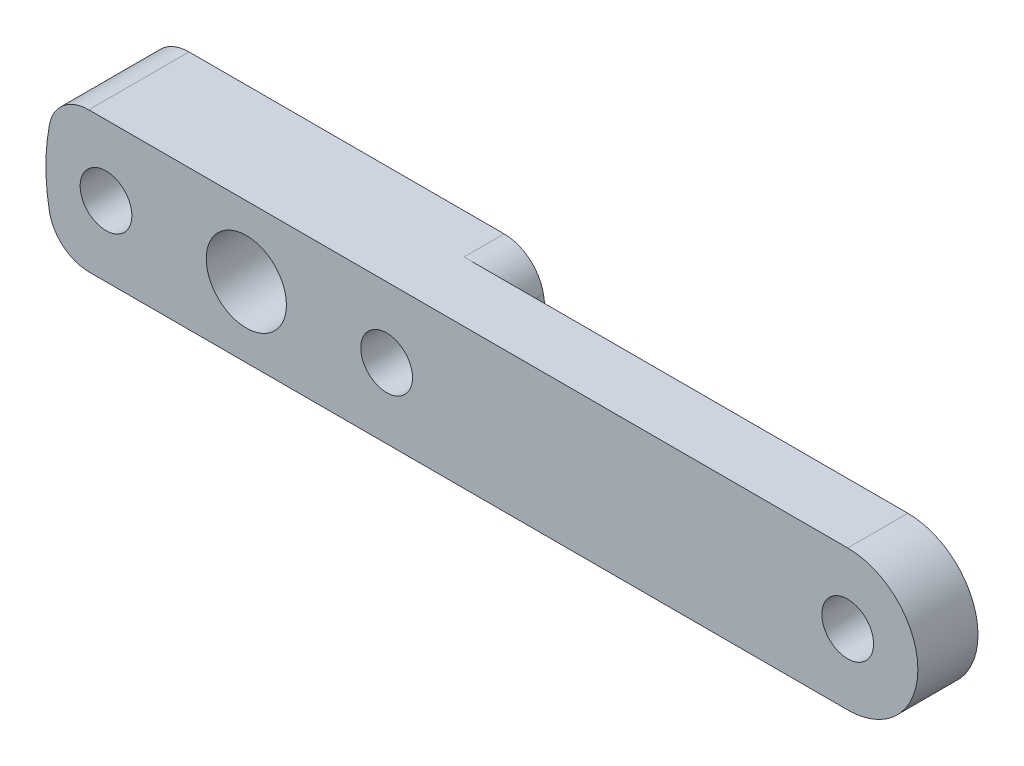
SolidWorks part; units mm, degrees
ref_plane "Front Plane" through (0, 0, 0) normal (0, 0, 1) x (1, 0, 0)
ref_plane "Top Plane" through (0, 0, 0) normal (0, 1, 0) x (1, 0, 0)
ref_plane "Right Plane" through (0, 0, 0) normal (1, 0, 0) x (0, 0, -1)
sketch "Sketch1" plane through (0, 0, 0) normal (0, 0, 1) x (1, 0, 0)
  line L0 (-9.3675, 3.5) -> (30, 3.5)
  line L1 (30, -3.5) -> (-9.3675, -3.5)
  line L2 (-7, 0) -> (7, 0) construction
  arc A0 (-9.3675, -3.5) -> (-9.3675, 3.5) centre (0, 0) cw
  arc A1 (30, 3.5) -> (30, -3.5) centre (30, 0) cw
  circle A2 centre (-7, 0) radius 1.29
  circle A3 centre (7, 0) radius 1.29
  circle A4 centre (30, 0) radius 1.29
  circle A5 centre (0, 0) radius 2
  point P6 (-10, 0)
  point P12 (0, 0)
  dimension "D1" = 10
  dimension "D2" = 7
  dimension "D4" = 2.58
  dimension "D6" = 4
  dimension "D3" = 30
  dimension "D5" = 14
extrude "Boss-Extrude1" add sketch "Sketch1" along normal mid plane 5
sketch "Sketch2" plane through (0, 0, -2.5) normal (0, 0, -1) x (-1, 0, 0)
  line L0 (9.3675, -3.5) -> (-30, -3.5) construction
  line L1 (-30, 3.5) -> (9.3675, 3.5) construction
  line L2 (-30, 3.5) -> (-9.3675, 3.5)
  line L3 (-9.3675, -3.5) -> (-30, -3.5)
  arc A0 (-30, 3.5) -> (-30, -3.5) centre (-30, 0) ccw construction
  arc A1 (-30, 3.5) -> (-30, -3.5) centre (-30, 0) ccw
  arc A2 (-9.3675, -3.5) -> (-9.3675, 3.5) centre (0, 0) cw
  point P4 (0, 0)
  dimension "D1" = 10
extrude "Cut-Extrude1" cut sketch "Sketch2" against normal offset from surface (2 mm away) 3 up to face at (11.0331, 0, 2.5)
fillet "Fillet1" radius 2 4 edges at (-9.3675, -3.5, 0) (-9.3675, 3.5, 0) (9.3675, -3.5, -1.5) (9.3675, 3.5, -1.5)
